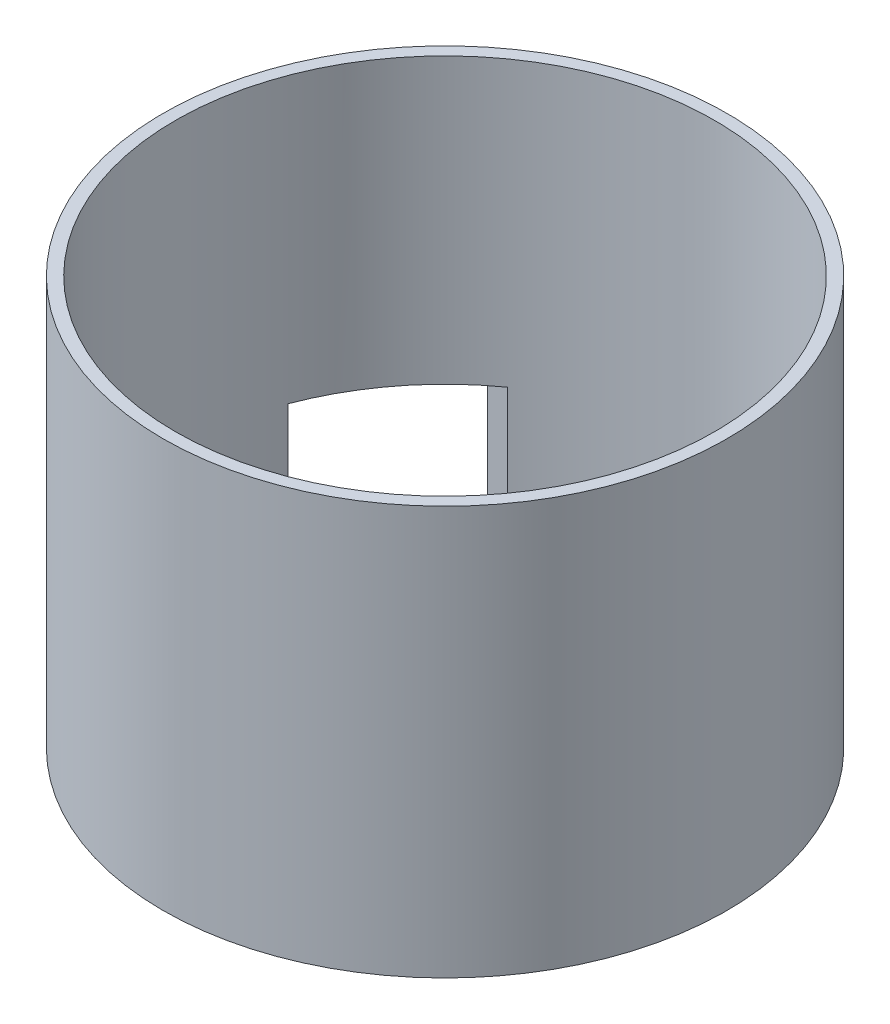
SolidWorks part; units mm, degrees
ref_plane "Front Plane" through (0, 0, 0) normal (0, 0, 1) x (1, 0, 0)
ref_plane "Top Plane" through (0, 0, 0) normal (0, 1, 0) x (1, 0, 0)
ref_plane "Right Plane" through (0, 0, 0) normal (1, 0, 0) x (0, 0, -1)
sketch "Sketch1" plane through (0, 0, 0) normal (0, 1, 0) x (1, 0, 0)
  circle A0 centre (0, 0) radius 69
  circle A1 centre (0, 0) radius 66
  dimension "D1" = 138
  dimension "D2" = 3
extrude "Boss-Extrude1" add sketch "Sketch1" along normal blind 100
sketch "Sketch2" plane through (0, 0, 0) normal (0, 1, 0) x (1, 0, 0)
  line L0 (0, 0) -> (-101.9987, 0) construction
  line L1 (0, 0) -> (-86.7855, -58.5376) construction
  line L2 (-62.1778, -41.9395) -> (-81.9858, -12.573) construction
  dimension "D1" = 34
  dimension "D2" = 75
ref_plane "Plane1" through (-62.1778, 0, 41.9395) normal (0.829, 0, -0.5592) x (-0.5592, 0, -0.829)
sketch "Sketch3" plane through (-62.1778, 0, 41.9395) normal (0.829, 0, -0.5592) x (-0.5592, 0, -0.829)
  line L0 (10, 38.5) -> (10, 66.5)
  line L1 (10, 66.5) -> (-10, 66.5)
  line L2 (-10, 66.5) -> (-10, 38.5)
  line L3 (-10, 38.5) -> (10, 38.5)
  point P2 (0, 38.5)
  dimension "D1" = 20
  dimension "D2" = 38.5
  dimension "D3" = 28
  dimension "D4" = 0
extrude "Cut-Extrude1" cut sketch "Sketch3" along normal up to next
fillet "Fillet1" radius 3 4 edges at (-49.7503, 38.5, 45.6192) (-60.9341, 38.5, 29.0384) (-49.7503, 66.5, 45.6192) (-60.9341, 66.5, 29.0384)
sketch "Sketch4" plane through (0, 0, 0) normal (1, 0, 0) x (0, 0, -1)
  line L1 (23.3, 0) -> (53.7, 0)
  line L2 (23.3, 0) -> (23.3, 30.4)
  line L3 (23.3, 30.4) -> (53.7, 30.4)
  line L4 (53.7, 0) -> (53.7, 30.4)
  dimension "D1" = 30.4
  dimension "D2" = 30.4
  dimension "D3" = 0
  dimension "D4" = 23.3
extrude "Cut-Extrude2" cut sketch "Sketch4" against normal through all
